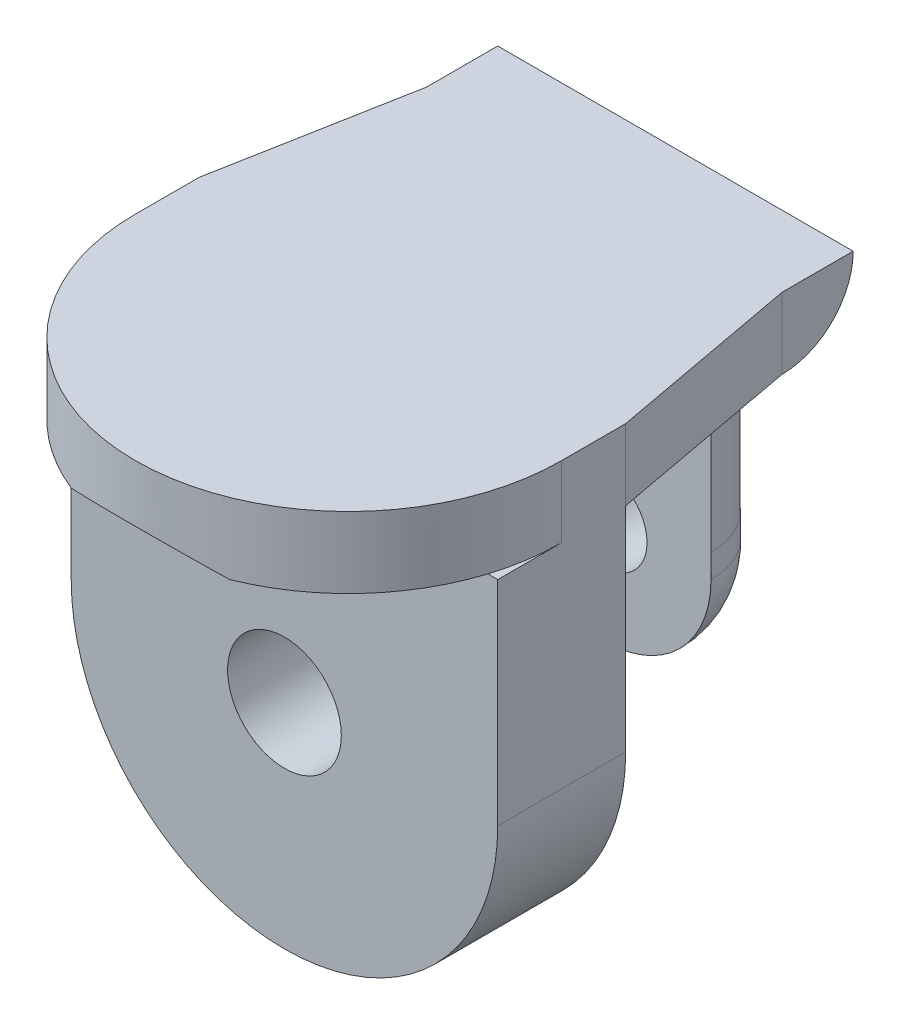
SolidWorks part; units mm, degrees
ref_plane "Front Plane" through (0, 0, 0) normal (0, 0, 1) x (1, 0, 0)
ref_plane "Top Plane" through (0, 0, 0) normal (0, 1, 0) x (1, 0, 0)
ref_plane "Right Plane" through (0, 0, 0) normal (1, 0, 0) x (0, 0, -1)
sketch "Sketch1" plane through (0, 0, 0) normal (0, 1, 0) x (1, 0, 0)
  circle A0 centre (0, 0) radius 15
  dimension "D1" = 30
extrude "Boss-Extrude1" add sketch "Sketch1" along normal blind 30
sketch "Sketch8" plane through (0, 30, 0) normal (0, 1, 0) x (1, 0, 0)
  line L0 (-16.5, 0) -> (16.5, 0) construction
  line L1 (15, 0) -> (-15, 0)
  line L2 (15, 0) -> (15, -15)
  line L3 (15, -15) -> (-15, -15)
  line L4 (-15, 0) -> (-15, -15)
  circle A0 centre (0, 0) radius 15 construction
  dimension "D1" = 15
  dimension "D2" = 30
revolve "Revolve1" add sketch "Sketch8" angle 180 about L1
sketch "Sketch9" plane through (0, 30, 0) normal (0, -1, 0) x (1, 0, 0)
  line L1 (15, 15) -> (-15, 15)
  line L2 (15, 15) -> (15, -15)
  line L3 (15, -15) -> (-15, -15)
  line L4 (-15, 15) -> (-15, -15)
extrude "Boss-Extrude3" add sketch "Sketch9" along normal blind 15
sketch "Sketch10" plane through (15, 0, 0) normal (1, 0, 0) x (0, 0, -1)
  circle A0 centre (0, 30) radius 5
  dimension "D1" = 10
extrude "Cut-Extrude1" cut sketch "Sketch10" against normal blind 30
ref_plane "Plane1" through (5, 0, 0) normal (1, 0, 0) x (0, 0, -1)
sketch "Sketch13" plane through (5, 0, 0) normal (1, 0, 0) x (0, 0, -1)
  line L0 (0, 16.5) -> (0, -16.5) construction
  line L1 (15, 15) -> (0, 15) construction
  circle A0 centre (0, 30) radius 16
  dimension "D1" = 32
  dimension "D2" = 15
extrude "Cut-Extrude2" cut sketch "Sketch13" against normal blind 10
sketch "Sketch14" plane through (0, 0, 15) normal (0, 0, 1) x (1, 0, 0)
  line L0 (5, -16.5) -> (5, 16.5) construction
  line L1 (-5, 30) -> (5, 30)
  line L2 (-5, 30) -> (-5, 15)
  line L3 (-5, 15) -> (5, 15)
  line L4 (5, 30) -> (5, 15)
  line L5 (0, 15) -> (15, 15) construction
extrude "Cut-Extrude3" cut sketch "Sketch14" against normal blind 67
sketch "Sketch15" plane through (-15, 0, 0) normal (-1, 0, 0) x (0, 0, 1)
  circle A0 centre (0, 30) radius 5 construction
  circle A1 centre (0, 30) radius 5
  circle A2 centre (0, 30) radius 11
  dimension "D1" = 22
extrude "Cut-Extrude4" cut sketch "Sketch15" against normal blind 7
sketch "Sketch16" plane through (15, 0, 0) normal (1, 0, 0) x (0, 0, -1)
  circle A0 centre (0, 30) radius 5 construction
  circle A1 centre (0, 30) radius 5
  circle A2 centre (0, 30) radius 11
  dimension "D1" = 22
extrude "Cut-Extrude5" cut sketch "Sketch16" against normal blind 7
ref_plane "Plane2" through (-31, 0, 0) normal (-1, 0, 0) x (0, 0, 1)
sketch "Sketch17" plane through (-31, 0, 0) normal (-1, 0, 0) x (0, 0, 1)
  line L0 (-15, 30) -> (-15, 15)
  line L1 (-15, 15) -> (0, 15)
  line L2 (0, 15) -> (15, 15)
  line L3 (15, 15) -> (15, 30)
  circle A2 centre (0, 30) radius 3.5
  circle A3 centre (0, 30) radius 11 construction
  circle A4 centre (0, 30) radius 8
  circle A5 centre (0, 30) radius 15
  arc A6 (-15, 30) -> (0, 15) centre (0, 30) ccw
  arc A7 (15, 30) -> (0, 15) centre (0, 30) cw
  dimension "D1" = 7
  dimension "D2" = 16
extrude "Boss-Extrude4" add sketch "Sketch17" along normal blind 2 separate body contours A4 A2 | A5 A4 | A5 L0 L1 | A5 L2 L3
sketch "Sketch18" plane through (-33, 0, 0) normal (-1, 0, 0) x (0, 0, 1)
  line L0 (8.5, 30) -> (8.5, 15)
  line L1 (-15, 15) -> (15, 15) construction
  line L2 (8.5, 15) -> (-8.5, 15)
  line L3 (-8.5, 15) -> (-8.5, 30)
  circle A2 centre (0, 30) radius 8.5
  dimension "D1" = 17
extrude "Boss-Extrude5" add sketch "Sketch18" along normal blind 5
sketch "Sketch20" plane through (-15, 0, 0) normal (-1, 0, 0) x (0, 0, 1)
  line L0 (-11.5, 30) -> (-15, 30)
  line L1 (-15, 30) -> (-15, 15)
  line L2 (-15, 15) -> (15, 15)
  line L3 (15, 15) -> (14.1421, 15) construction
  line L4 (-15, 15) -> (-8.5, 15) construction
  line L5 (15, 15) -> (15, 30)
  line L6 (15, 15) -> (15, 30) construction
  line L7 (15, 30) -> (11.5, 30)
  circle A0 centre (0, 30) radius 11.5
  line M4 (-15, 30) -> (-15, 15)
  line M5 (-15, 15) -> (0, 15)
  line M6 (0, 15) -> (15, 15)
  line M7 (15, 15) -> (15, 30)
  dimension "D1" = 23
extrude "Boss-Extrude6" add sketch "Sketch20" along normal blind 16 contours A0 L0 L7 M4 M5 M6 M7
sketch "Sketch21" plane through (0, 15, 0) normal (0, -1, 0) x (1, 0, 0)
  line L1 (15, 15) -> (-38, 15)
  line L2 (15, 15) -> (15, -15)
  line L3 (15, -15) -> (-38, -15)
  line L4 (-38, 15) -> (-38, -15)
extrude "Cut-Extrude7" cut sketch "Sketch21" along normal blind 20
ref_plane "Plane3" through (0, 0, 0) normal (0, -1, 0) x (-1, 0, 0)
sketch "Sketch23" plane through (0, 0, 0) normal (0, -1, 0) x (-1, 0, 0)
  line L0 (-15, -4.5) -> (0, -4.5)
  line L1 (-15, -4.5) -> (-15, 4.5)
  line L2 (0, -4.5) -> (0, 4.5)
  line L3 (-15, 4.5) -> (0, 4.5)
  line L4 (-15, 15) -> (-15, -15) construction
  line L5 (0, 16.5) -> (0, -16.5) construction
  line L6 (-16.5, 0) -> (16.5, 0) construction
  dimension "D1" = 9
  dimension "D2" = 4.5
revolve "Revolve2" add sketch "Sketch23" angle 360 about L2
sketch "Sketch24" plane through (0, 15, 0) normal (0, -1, 0) x (1, 0, 0)
  line L1 (-15, 4.5) -> (15, 4.5)
  line L2 (-15, 4.5) -> (-15, -4.5)
  line L3 (-15, -4.5) -> (15, -4.5)
  line L4 (15, 4.5) -> (15, -4.5)
extrude "Boss-Extrude7" add sketch "Sketch24" along normal blind 15
sketch "Sketch25" plane through (0, 0, 4.5) normal (0, 0, 1) x (1, 0, 0)
  circle A0 centre (0, 0) radius 4
  dimension "D1" = 8
extrude "Cut-Extrude8" cut sketch "Sketch25" against normal blind 15
sketch "Sketch26" plane through (0, 0, -15) normal (0, 0, -1) x (-1, 0, 0)
  line L0 (-16.5, 0) -> (16.5, 0) construction
  line L1 (-15, 30) -> (15, 30)
  line L2 (-15, 30) -> (-15, 15)
  line L3 (-15, 15) -> (-12.5, 15)
  line L4 (15, 30) -> (15, 15)
  line L6 (-7.5, 10) -> (-7.5, 0)
  line L7 (-7.5, 0) -> (7.5, 0)
  line L8 (7.5, 10) -> (7.5, 0)
  line L9 (-5, 15) -> (-15, 15) construction
  line L10 (12.5, 15) -> (15, 15)
  line L11 (38, 15) -> (5, 15) construction
  line L12 (15, 30) -> (15, 45) construction
  circle A0 centre (0, 0) radius 7.5
  circle A1 centre (0, 0) radius 3
  arc A2 (-7.5, 10) -> (-12.5, 15) centre (-12.5, 10) ccw
  arc A3 (12.5, 15) -> (7.5, 10) centre (12.5, 10) ccw
  line M13 (-15, 15) -> (-5, 15)
  line M14 (-5, 15) -> (-5, 30)
  line M15 (-5, 30) -> (-15, 30)
  line M16 (-15, 30) -> (-15, 15)
  dimension "D1" = 6
  dimension "D2" = 15
  dimension "D3" = 5
  dimension "D4" = 5
extrude "Boss-Extrude8" add sketch "Sketch26" along normal blind 5 from offset 3 contours M16 M13 M14 M15 | A3 L10 L4 L1 A2 L6 A0 L8 M14 M13 | A1 L7 A0 | A1 L7 A0
sketch "Sketch30" plane through (0, 0, -18) normal (0, 0, 1) x (1, 0, 0)
  line L1 (15, 30) -> (-15, 30)
  line L2 (15, 30) -> (15, 15)
  line L3 (15, 15) -> (-15, 15)
  line L4 (-15, 30) -> (-15, 15)
extrude "Boss-Extrude9" add sketch "Sketch30" along normal blind 3
sketch "Sketch27" plane through (0, 0, 4.5) normal (0, 0, 1) x (1, 0, 0)
  circle A0 centre (0, 0) radius 16
  dimension "D1" = 32
extrude "Cut-Extrude9" cut sketch "Sketch27" along normal blind 16
sketch "Sketch28" plane through (0, 0, -4.5) normal (0, 0, -1) x (-1, 0, 0)
  circle A0 centre (0, 0) radius 16
  dimension "D1" = 32
extrude "Cut-Extrude10" cut sketch "Sketch28" along normal blind 10.5
sketch "Sketch29" plane through (5, 0, 0) normal (-1, 0, 0) x (0, 0, 1)
  line L0 (0, -29.15) -> (0, 29.15) construction
  circle A0 centre (0, 30) radius 16
  arc A1 (15, 30) -> (-15, 30) centre (0, 30) ccw construction
  dimension "D1" = 32
extrude "Cut-Extrude12" cut sketch "Sketch29" along normal blind 10
sketch "Sketch31" plane through (0, 15, 0) normal (0, -1, 0) x (1, 0, 0)
  line L0 (-38, 15) -> (15, 15)
  line L1 (-38, 15) -> (-38, -26.4967)
  line L2 (15, 15) -> (15, -26.4967)
  line L3 (-38, -26.4967) -> (15, -26.4967)
extrude "Cut-Extrude13" cut sketch "Sketch31" against normal blind 37
sketch "Sketch33" plane through (0, 15, 0) normal (0, 1, 0) x (1, 0, 0)
  line L0 (-12.5, 23) -> (-12.5, 18)
  line L1 (-12.5, 18) -> (-15, 4.5)
  line L2 (-15, 4.5) -> (-15, 0)
  line L3 (-15, -4.5) -> (-15, 4.5) construction
  line L4 (-12.5, 23) -> (12.5, 23)
  line L5 (12.5, 23) -> (12.5, 18)
  line L6 (12.5, 18) -> (15, 4.5)
  line L7 (15, 4.5) -> (15, -4.5) construction
  line L9 (15, 4.5) -> (15, 0)
  arc A0 (15, 0) -> (-15, 0) centre (0, 0) cw
  line M1 (-15, 4.5) -> (-15, -4.5)
  line M2 (-15, -4.5) -> (-5, -4.5)
  line M3 (-5, -4.5) -> (-5, 4.5)
  line M4 (-5, 4.5) -> (-15, 4.5)
extrude "Boss-Extrude10" add sketch "Sketch33" along normal blind 5 contours A0 L9 L6 L5 L4 L0 L1 M4 M3 M2 | A0 M2 M3 M4 M1
sketch "Sketch35" plane through (0, 15, 0) normal (0, -1, 0) x (1, 0, 0)
  line L1 (-15, 4.5) -> (15, 4.5)
  line L2 (-15, 4.5) -> (-15, -4.5)
  line L3 (-15, -4.5) -> (15, -4.5)
  line L4 (15, 4.5) -> (15, -4.5)
extrude "Boss-Extrude11" add sketch "Sketch35" along normal blind 5
sketch "Sketch36" plane through (0, 0, -4.5) normal (0, 0, -1) x (-1, 0, 0)
  circle A0 centre (0, 0) radius 16
  dimension "D1" = 32
extrude "Cut-Extrude14" cut sketch "Sketch36" along normal blind 13.5
sketch "Sketch37" plane through (0, 0, 4.5) normal (0, 0, 1) x (1, 0, 0)
  circle A0 centre (0, 0) radius 16
  dimension "D1" = 32
extrude "Cut-Extrude15" cut sketch "Sketch37" along normal blind 18.5
fillet "Fillet1" radius 5 4 edges at (-8.9645, 13.5355, -23) (8.9645, 13.5355, -23) (7.5, 5, -23) (-7.5, 5, -23)
